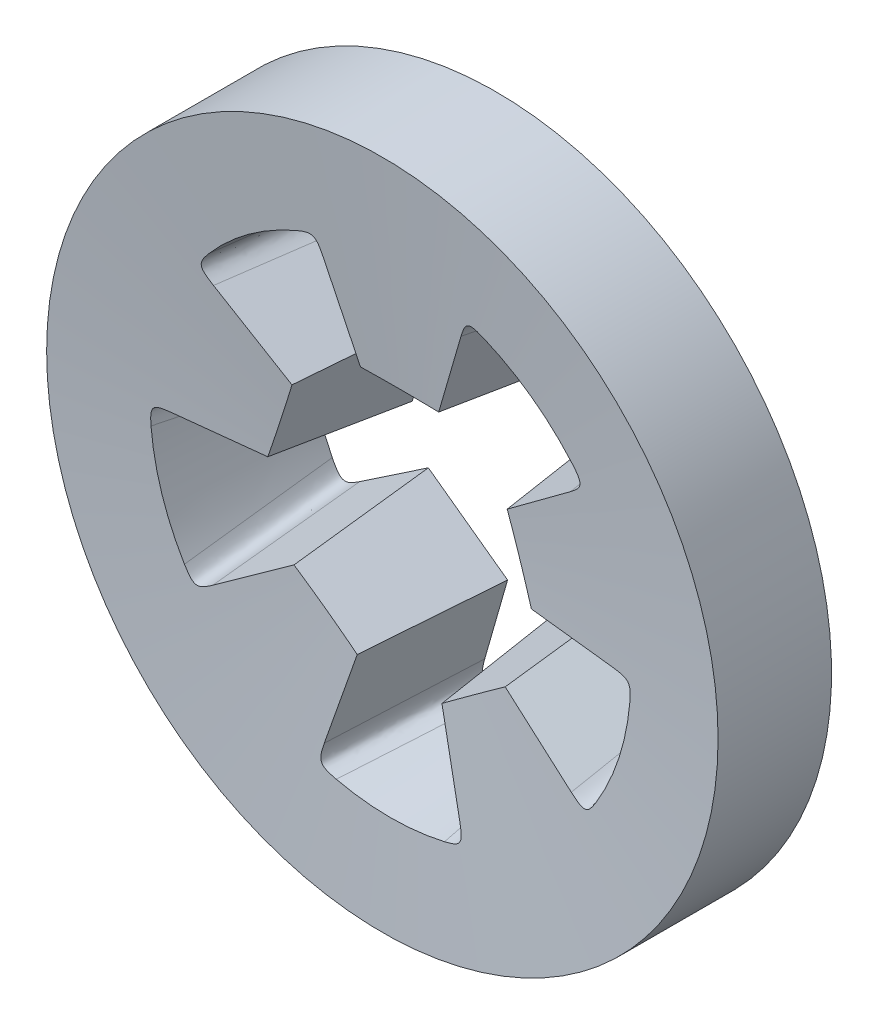
SolidWorks part; units mm, degrees
ref_plane "Front Plane" through (0, 0, 0) normal (0, 0, 1) x (1, 0, 0)
ref_plane "Top Plane" through (0, 0, 0) normal (0, 1, 0) x (1, 0, 0)
ref_plane "Right Plane" through (0, 0, 0) normal (1, 0, 0) x (0, 0, -1)
sketch "Sketch1" plane through (0, 0, 0) normal (0, 0, 1) x (1, 0, 0)
  circle A0 centre (0, 0) radius 17.75
  dimension "D1" = 35.5
extrude "Boss-Extrude1" add sketch "Sketch1" along normal blind 8
sketch "Sketch2" plane through (0, 0, 8) normal (0, 0, 1) x (1, 0, 0)
  line L0 (-2, 6.75) -> (2, 6.75)
  line L1 (0, 0) -> (0, 22.5506) construction
  line L2 (2, 6.75) -> (3.9549, 12.1211)
  line L3 (-2, 6.75) -> (-3.9549, 12.1211)
  line L4 (5.8016, 3.988) -> (7.0377, 0.1838)
  line L5 (7.0377, 0.1838) -> (12.75, -0.0157)
  line L6 (5.8016, 3.988) -> (10.3057, 7.507)
  line L7 (5.5856, -4.2853) -> (2.3495, -6.6364)
  line L8 (2.3495, -6.6364) -> (3.925, -12.1308)
  line L9 (5.5856, -4.2853) -> (10.3242, -7.4815)
  line L10 (-2.3495, -6.6364) -> (-5.5856, -4.2853)
  line L11 (-5.5856, -4.2853) -> (-10.3242, -7.4815)
  line L12 (-2.3495, -6.6364) -> (-3.925, -12.1308)
  line L13 (-7.0377, 0.1838) -> (-5.8016, 3.988)
  line L14 (-5.8016, 3.988) -> (-10.3057, 7.507)
  line L15 (-7.0377, 0.1838) -> (-12.75, -0.0157)
  circle A0 centre (0, 0) radius 12.75
  circle A1 centre (0, 0) radius 17.75 construction
  point P12 (0, 12.75)
  point P26 (0, 0)
  point P30 (2.7528, -2)
  point P31 (0, 0)
  dimension "D1" = 5
  dimension "D2" = 4
  dimension "D3" = 2
  dimension "D4" = 110
  dimension "D5" = 110
  dimension "D6" = 6
  dimension "D7" = 5
extrude "Cut-Extrude1" cut sketch "Sketch2" against normal blind 11 draft 6 contours A0 L2 L0 L3 region at (0, 0, 8)
sketch "Sketch3" plane through (0, 0, 0) normal (1, 0, 0) x (0, 0, -1)
  line L0 (10.1673, 0) -> (-29.1737, 0) construction
  line L1 (-23.7457, 17.75) -> (8.6762, 17.75) construction
  line L2 (-11.5536, 21.75) -> (1.907, 21.75) construction
  line L3 (-8, 17.75) -> (-6.5, 0)
  line L4 (-6.5, 0) -> (-8, 0)
  line L5 (-8, 0) -> (-8, 17.75)
  line L6 (-8, 17.75) -> (-8, -17.75) construction
  dimension "D1" = 4
  dimension "D2" = 1.5
  dimension "D3" = 0
revolve "Cut-Revolve1" cut sketch "Sketch3" angle 360 about L0
fillet "Fillet1" radius 1 10 edges conic rho 0.65
sketch "Sketch4" plane through (0, 0, 0) normal (0, 0, -1) x (-1, 0, 0)
  circle A0 centre (0, 0) radius 13.9092
  arc A1 (8.3618, 8.4799) -> (5.4809, 10.573) centre (0, 0) ccw construction
  circle A2 centre (0, 0) radius 17.75
  dimension "D1" = 2
extrude "Cut-Extrude2" cut sketch "Sketch4" against normal blind 2
sketch "Sketch5" plane through (0, 0, 0) normal (0, 0, -1) x (-1, 0, 0)
  circle A0 centre (0, 11.7434) radius 2.5
  point P2 (0, 11.7434)
extrude "Cut-Extrude3" cut sketch "Sketch5" against normal blind 5
sketch "Sketch6" plane through (0, 0, 0) normal (0, 0, -1) x (-1, 0, 0)
  circle A0 centre (0, 11.7434) radius 3
extrude "Cut-Extrude4" cut sketch "Sketch6" against normal blind 1.5
pattern_circular "CirPattern1" count 5 over 360 about axis through (0, 0, 0) along (0, 0, -1) of "Cut-Extrude3", "Cut-Extrude4"
